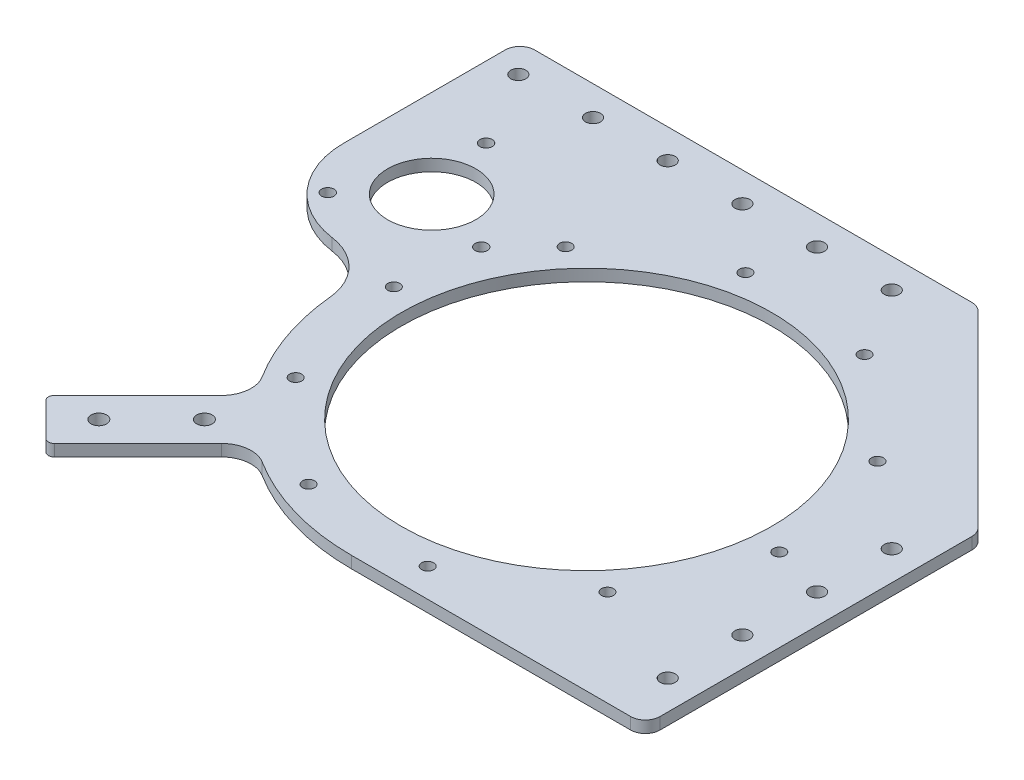
SolidWorks part; units mm, degrees
material "1060 合金"
ref_plane "前视基准面" through (0, 0, 0) normal (0, 0, 1) x (1, 0, 0)
ref_plane "上视基准面" through (0, 0, 0) normal (0, 1, 0) x (1, 0, 0)
ref_plane "右视基准面" through (0, 0, 0) normal (1, 0, 0) x (0, 0, -1)
sketch "草图1" plane through (0, 0, 0) normal (0, 1, 0) x (1, 0, 0)
  line L1 (80, 80) -> (-80, 80)
  line L2 (80, 80) -> (80, -80)
  line L3 (80, -80) -> (-80, -80)
  line L4 (-80, 80) -> (-80, -80)
  line L5 (80, 80) -> (-80, -80) construction
  line L6 (80, -80) -> (-80, 80) construction
  line L7 (-33.1371, 80) -> (-80, 33.1371)
  circle A0 centre (0, 0) radius 63
  circle A1 centre (0, 0) radius 80
  dimension "D1" = 126
  dimension "D2" = 160
  dimension "D3" = 160
  dimension "D6" = 80
extrude "凸台-拉伸1" add sketch "草图1" along normal blind 4 contours A1 L4 L3 | A1 A0 | A1 L7 L4 | A1 L1 L7 | A1 L2 L1
sketch "草图2" plane through (0, 4, 0) normal (0, 1, 0) x (1, 0, 0)
  line L0 (80, 80) -> (-33.1371, 80) construction
  line L1 (87.6748, 80) -> (80, 80)
  line L2 (80, 80) -> (80, 67.1954)
  line L3 (80, 80) -> (80, 0) construction
  line L4 (80, 67.1954) -> (80, 10)
  line L5 (92.6653, 10) -> (80, 10)
  line L6 (87.6748, 80) -> (122.6653, 80)
  line L7 (122.6653, 80) -> (122.6653, 40)
  circle A0 centre (92.6653, 40) radius 11.2
  circle A1 centre (92.6653, 40) radius 30
  circle A2 centre (92.6653, 40) radius 9.5
  dimension "D2" = 40
  dimension "D3" = 22.4
  dimension "D4" = 19
  dimension "D5" = 60
  dimension "D1" = 100.93
  dimension "D6" = 30
extrude "凸台-拉伸2" add sketch "草图2" against normal up to surface (4 mm away) separate body
combine bodies "组合5" operation type add bodies to combine 106 107
sketch "草图3" plane through (0, 4, 0) normal (0, 1, 0) x (1, 0, 0)
  line L0 (92.6653, 40) -> (98.4887, 64.3123)
  line L1 (122.6653, 80) -> (-33.1371, 80) construction
  circle A0 centre (92.6653, 40) radius 25
  circle A1 centre (98.4887, 64.3123) radius 2.1
  circle A2 centre (110.8087, 22.8006) radius 2.1
  circle A3 centre (68.6986, 32.8871) radius 2.1
  dimension "D1" = 50
  dimension "D3" = 4.2
  dimension "D5" = 25
  dimension "D6" = 25
  dimension "D2" = 76.53
  dimension "D4" = 3
extrude "切除-拉伸1" cut sketch "草图3" against normal blind 10 contours A0 A3 | A0 A3 | A0 A2 | A0 A2 | L0 A1 A0 | A0 A1 | A0 A1 L0
sketch "草图4" plane through (0, 4, 0) normal (0, 1, 0) x (1, 0, 0)
  line L0 (-71.8256, -6.2839) -> (0, 0)
  line L1 (-80, 33.1371) -> (-80, -80) construction
  circle A0 centre (0, 0) radius 72.1
  circle A1 centre (0, 0) radius 63 construction
  circle A2 centre (-71.8256, -6.2839) radius 2.05
  dimension "D1" = 9.1
  dimension "D2" = 4.1
  dimension "D3" = 95
extrude "切除-拉伸2" cut sketch "草图4" against normal blind 10 contours A0 A2 L0 | L0 A2 A0 | A0 A2
pattern_circular "阵列(圆周)1" count 10 over 360 about axis through (0, 0, 0) along (0, 1, 0) of "切除-拉伸2"
sketch "草图5" plane through (0, 4, 0) normal (0, 1, 0) x (1, 0, 0)
  line L0 (-100, 33.1371) -> (-33.1371, 100)
  line L1 (-80, -80) -> (-100, -80)
  line L2 (-80, -80) -> (-80, 33.1371)
  line L3 (-80, 33.1371) -> (-100, 33.1371)
  line L4 (-100, -80) -> (-100, 33.1371)
  line L5 (-33.1371, 80) -> (122.6653, 80)
  line L6 (-33.1371, 80) -> (-33.1371, 100)
  line L7 (-33.1371, 100) -> (122.6653, 100)
  line L8 (122.6653, 80) -> (122.6653, 100)
  line L9 (122.6653, 40) -> (122.6653, 80) construction
  line M22 (122.6653, 80) -> (-33.1371, 80)
  line M23 (-33.1371, 80) -> (-80, 33.1371)
  line M24 (-80, 33.1371) -> (-80, -80)
  dimension "D1" = 20
  dimension "D2" = 20
  dimension "D3" = 0
  dimension "D4" = 0
extrude "凸台-拉伸3" add sketch "草图5" against normal blind 4 contours L4 L1 L3 M24 | L6 L0 L3 M23 | L5 L8 L7 L6 M22
sketch "草图6" plane through (0, 4, 0) normal (0, 1, 0) x (1, 0, 0)
  line L0 (-43.1371, 90) -> (122.6653, 90)
  line L1 (-100, 33.1371) -> (-33.1371, 100) construction
  line L2 (122.6653, 100) -> (122.6653, 40) construction
  line L3 (-33.1371, 100) -> (122.6653, 100) construction
  line L4 (-90, 43.1371) -> (-90, -80)
  line L5 (0, -80) -> (-100, -80) construction
  line L6 (-100, -80) -> (-100, 33.1371) construction
  line L7 (-90, 43.1371) -> (-90, 90)
  line L8 (-90, 90) -> (-43.1371, 90)
  circle A1 centre (-90, 90) radius 2.55
  circle A2 centre (-64.6, 90) radius 2.55
  circle A3 centre (-39.2, 90) radius 2.55
  circle A4 centre (-13.8, 90) radius 2.55
  circle A5 centre (11.6, 90) radius 2.55
  circle A6 centre (37, 90) radius 2.55
  circle A7 centre (62.4, 90) radius 2.55
  circle A8 centre (87.8, 90) radius 2.55
  circle A9 centre (113.2, 90) radius 2.55
  circle A10 centre (138.6, 90) radius 2.55
  circle A11 centre (-90, 64.6) radius 2.55
  circle A12 centre (-90, 39.2) radius 2.55
  circle A13 centre (-90, 13.8) radius 2.55
  circle A14 centre (-90, -11.6) radius 2.55
  circle A15 centre (-90, -37) radius 2.55
  circle A16 centre (-90, -62.4) radius 2.55
  dimension "D3" = 5.1
  dimension "D1" = 10
  dimension "D2" = 10
  dimension "D4" = 10
  dimension "D5" = 7
extrude "切除-拉伸3" cut sketch "草图6" against normal blind 10 contours L4 A13 | L4 A13 | L4 A14 | L4 A15 | L4 A15 | L4 A16 | L4 A16 | L0 A4 | L0 A4 | L0 A5 | L0 A5 | L0 A6 | L0 A6 | L0 A7 | L0 A7 | L0 A8 | L0 A8 | L0 A9 | L0 A9 | L4 A14
fillet "圆角1" radius 20 1 edges at (80, 2, -10)
sketch "草图7" plane through (0, 4, 0) normal (0, 1, 0) x (1, 0, 0)
  circle A0 centre (92.6653, 40) radius 15
  dimension "D1" = 30
extrude "切除-拉伸4" cut sketch "草图7" against normal blind 10
fillet "圆角2" radius 5 4 edges at (122.6653, 2, -100) (-33.1371, 2, -100) (-100, 2, 80) (-100, 2, -33.1371)
ref_plane "基准面1" through (132.6653, 0, 0) normal (1, 0, 0) x (0, 0, -1)
mirror "镜向2" about plane through (132.6653, 0, 0) normal (1, 0, 0) of bodies 114
sketch "草图8" plane through (132.6653, 0, 0) normal (1, 0, 0) x (0, 0, -1)
  line L1 (154.2632, -59.3341) -> (-102.4156, -59.3341)
  line L2 (154.2632, -59.3341) -> (154.2632, 117.4629)
  line L3 (154.2632, 117.4629) -> (-102.4156, 117.4629)
  line L4 (-102.4156, -59.3341) -> (-102.4156, 117.4629)
  line L5 (154.2632, -59.3341) -> (-102.4156, 117.4629) construction
  line L6 (154.2632, 117.4629) -> (-102.4156, -59.3341) construction
  point P0 (25.9238, 29.0644)
extrude "切除-拉伸5" cut sketch "草图8" against normal blind 290
sketch "草图9" plane through (0, 4, 0) normal (0, 1, 0) x (1, 0, 0)
  line L0 (279.1307, 90) -> (355.3307, 13.8)
  line L1 (317.2307, 51.9) -> (118.8767, -146.454)
  line L2 (166.3357, -84.8528) -> (201.6911, -49.4975)
  line L3 (166.3357, -84.8528) -> (180.4779, -98.9949)
  line L4 (201.6911, -49.4975) -> (215.8332, -63.6396)
  line L5 (180.4779, -98.9949) -> (215.8332, -63.6396)
  line L6 (166.3357, -84.8528) -> (215.8332, -63.6396) construction
  line L7 (201.6911, -49.4975) -> (180.4779, -98.9949) construction
  line L8 (201.6911, -49.4975) -> (215.8332, -63.6396)
  line L9 (201.6911, -49.4975) -> (204.9617, -46.2269)
  line L10 (215.8332, -63.6396) -> (219.1038, -60.369)
  line L11 (204.9617, -46.2269) -> (219.1038, -60.369)
  arc A0 (185.6944, -7.6195) -> (265.3307, -80) centre (265.3307, 0) ccw construction
  point P7 (191.0845, -74.2462)
  arc M33 (185.6944, -7.6195) -> (265.3307, -80) centre (265.3307, 0) ccw
  dimension "D5" = 50
  dimension "D1" = 20
  dimension "D2" = 0
  dimension "D3" = 90
  dimension "D4" = 80
extrude "凸台-拉伸4" add sketch "草图9" against normal up to surface (4 mm away) contours L4 L2 L3 L1 | L3 L5 L4 L1 | L9 L4 M33 | L4 L10 M33
fillet "圆角3" radius 10 2 edges at (216.2769, 2, 63.1959) (202.1347, 2, 49.0538)
fillet "圆角4" radius 2 2 edges at (180.4779, 2, 98.9949) (166.3357, 2, 84.8528)
sketch "草图10" plane through (0, 4, 0) normal (0, 1, 0) x (1, 0, 0)
  line L0 (173.4068, -91.9239) -> (265.3307, 0)
  line L1 (167.7499, -86.267) -> (179.0636, -97.5807) construction
  circle A0 centre (200.3476, -64.9831) radius 2.65
  circle A1 centre (182.3871, -82.9436) radius 2.65
  dimension "D1" = 5.3
  dimension "D2" = 5.3
  dimension "D3" = 12.7
  dimension "D4" = 25.4
extrude "切除-拉伸6" cut sketch "草图10" against normal blind 10 contours L0 A0 | L0 A0 | L0 A1 | L0 A1
